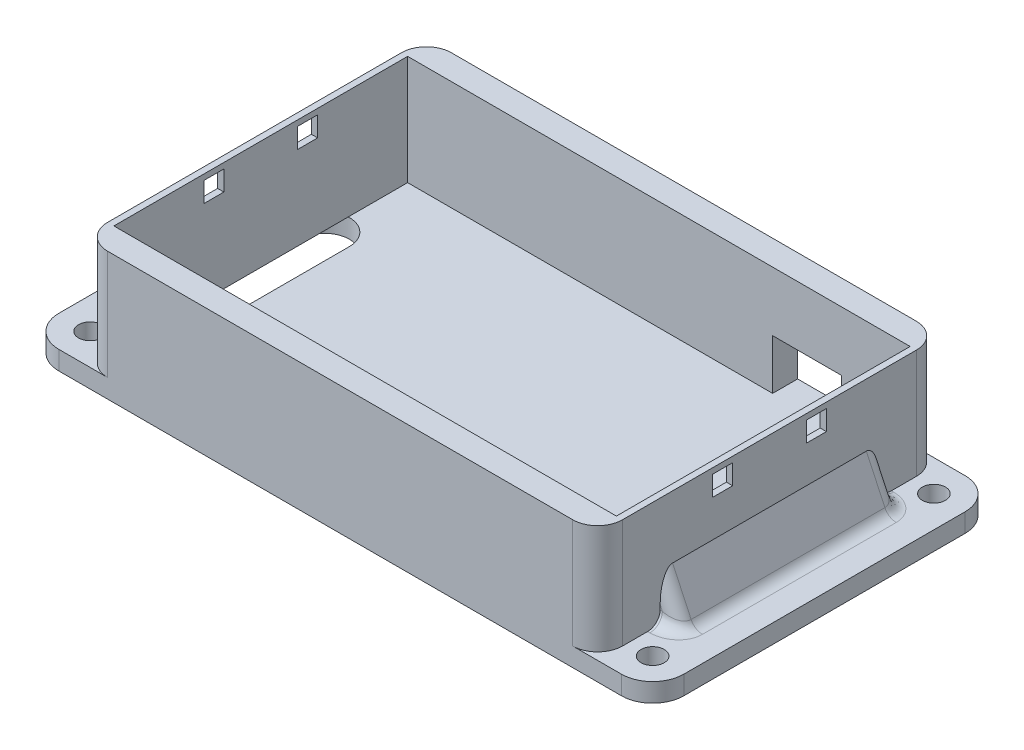
SolidWorks part; units mm, degrees
material "Copper"
ref_plane "Front Plane" through (0, 0, 0) normal (0, 0, 1) x (1, 0, 0)
ref_plane "Top Plane" through (0, 0, 0) normal (0, 1, 0) x (1, 0, 0)
ref_plane "Right Plane" through (0, 0, 0) normal (1, 0, 0) x (0, 0, -1)
sketch "Sketch1" plane through (0, 0, 0) normal (0, 1, 0) x (1, 0, 0)
  line L1 (6.35, 0) -> (120.65, 0)
  line L2 (0, 6.35) -> (0, 63.5)
  line L3 (6.35, 69.85) -> (120.65, 69.85)
  line L4 (127, 6.35) -> (127, 63.5)
  arc A0 (6.35, 0) -> (0, 6.35) centre (6.35, 6.35) cw
  arc A1 (120.65, 0) -> (127, 6.35) centre (120.65, 6.35) ccw
  arc A2 (120.65, 69.85) -> (127, 63.5) centre (120.65, 63.5) cw
  arc A3 (0, 63.5) -> (6.35, 69.85) centre (6.35, 63.5) cw
  point P7 (0, 0)
  point P10 (127, 0)
  point P13 (127, 69.85)
  point P16 (0, 69.85)
  dimension "D3" = 6.35
  dimension "D1" = 127
  dimension "D2" = 69.85
extrude "Base Extrude" add sketch "Sketch1" along normal blind 3.81
sketch "Sketch2" plane through (0, 3.81, 0) normal (0, 1, 0) x (1, 0, 0)
  line L0 (63.5, 69.85) -> (63.5, 0) construction
  line L1 (120.65, 69.85) -> (6.35, 69.85) construction
  line L2 (6.35, 0) -> (120.65, 0) construction
  line L3 (0, 34.925) -> (127, 34.925) construction
  line L4 (0, 63.5) -> (0, 6.35) construction
  line L5 (127, 6.35) -> (127, 63.5) construction
  line L6 (7.62, 34.925) -> (17.78, 34.925) construction
  line L8 (7.62, 47.625) -> (7.62, 22.225)
  line L10 (17.78, 47.625) -> (17.78, 22.225)
  line L11 (119.38, 47.625) -> (119.38, 22.225)
  line L12 (109.22, 47.625) -> (109.22, 22.225)
  circle A0 centre (6.35, 63.5) radius 2.3495
  circle A1 centre (6.35, 6.35) radius 2.3495
  arc A2 (17.78, 47.625) -> (7.62, 47.625) centre (12.7, 47.625) ccw
  arc A3 (7.62, 22.225) -> (17.78, 22.225) centre (12.7, 22.225) ccw
  circle A4 centre (120.65, 6.35) radius 2.3495
  circle A5 centre (120.65, 63.5) radius 2.3495
  arc A6 (109.22, 47.625) -> (119.38, 47.625) centre (114.3, 47.625) cw
  arc A7 (119.38, 22.225) -> (109.22, 22.225) centre (114.3, 22.225) cw
  dimension "D1" = 4.699
  dimension "D5" = 5.08
  dimension "D2" = 6.35
  dimension "D3" = 6.35
  dimension "D4" = 6.35
  dimension "D6" = 10.16
  dimension "D7" = 25.4
  dimension "D8" = 12.7
extrude "Hole Cuts" cut sketch "Sketch2" against normal through all
sketch "Sketch3" plane through (0, 3.81, 0) normal (0, 1, 0) x (1, 0, 0)
  line L0 (120.65, 69.85) -> (6.35, 69.85) construction
  line L1 (16.256, 69.85) -> (110.744, 69.85)
  line L2 (11.176, 64.77) -> (11.176, 5.08)
  line L3 (16.256, 0) -> (110.744, 0)
  line L4 (115.824, 64.77) -> (115.824, 5.08)
  line L5 (6.35, 0) -> (120.65, 0) construction
  line L6 (63.5, 69.85) -> (63.5, 0) construction
  line L7 (63.5, 0) -> (63.5, 69.85) construction
  line L9 (12.446, 64.77) -> (114.554, 64.77)
  line L10 (12.446, 64.77) -> (12.446, 5.08)
  line L11 (12.446, 5.08) -> (114.554, 5.08)
  line L12 (114.554, 64.77) -> (114.554, 5.08)
  arc A0 (110.744, 69.85) -> (115.824, 64.77) centre (110.744, 64.77) cw
  arc A1 (110.744, 0) -> (115.824, 5.08) centre (110.744, 5.08) ccw
  arc A2 (11.176, 5.08) -> (16.256, 0) centre (16.256, 5.08) ccw
  arc A3 (16.256, 69.85) -> (11.176, 64.77) centre (16.256, 64.77) ccw
  point P18 (115.824, 0)
  point P23 (11.176, 69.85)
  dimension "D6" = 5.08
  dimension "D1" = 104.648
  dimension "D2" = 1.27
  dimension "D3" = 1.27
  dimension "D4" = 5.08
  dimension "D5" = 5.08
extrude "Shell Extrude" add sketch "Sketch3" along normal blind 22.225
ref_plane "Shell Support Plane" through (0, 0, -34.925) normal (0, 0, 1) x (1, 0, 0)
sketch "Sketch4" plane through (0, 0, -34.925) normal (0, 0, 1) x (1, 0, 0)
  line L0 (11.176, 3.81) -> (6.731, 3.81)
  line L1 (6.731, 3.81) -> (11.176, 13.335)
  line L2 (11.176, 26.035) -> (11.176, 3.81) construction
  line L3 (11.176, 13.335) -> (11.176, 3.81)
  line L5 (63.5, 26.035) -> (63.5, 0) construction
  line L6 (16.256, 26.035) -> (110.744, 26.035) construction
  line L7 (6.35, 0) -> (120.65, 0) construction
  line L8 (115.824, 13.335) -> (115.824, 3.81)
  line L9 (120.269, 3.81) -> (115.824, 13.335)
  line L10 (115.824, 3.81) -> (120.269, 3.81)
  dimension "D1" = 4.445
  dimension "D2" = 9.525
extrude "Shell Support Extrude" add sketch "Sketch4" along normal blind 22.225 and the other way blind 22.225
fillet "Shell Support Fillet" radius 2.54 10 edges at (6.731, 3.81, -34.925) (8.9535, 3.81, -12.7) (8.9535, 8.5725, -12.7) (8.9535, 8.5725, -57.15) (8.9535, 3.81, -57.15) (118.0465, 8.5725, -57.15) (118.0465, 8.5725, -12.7) (118.0465, 3.81, -12.7) (120.269, 3.81, -34.925) (118.0465, 3.81, -57.15)
sketch "Sketch5" plane through (115.824, 0, 0) normal (1, 0, 0) x (0, 0, -1)
  line L0 (34.925, 26.035) -> (34.925, 0) construction
  line L1 (5.08, 26.035) -> (64.77, 26.035) construction
  line L2 (6.35, 0) -> (63.5, 0) construction
  line L3 (46.482, 24.892) -> (42.418, 20.828) construction
  line L4 (23.368, 20.828) -> (27.432, 20.828)
  line L5 (23.368, 20.828) -> (23.368, 24.892)
  line L6 (23.368, 24.892) -> (27.432, 24.892)
  line L7 (27.432, 20.828) -> (27.432, 24.892)
  line L8 (23.368, 20.828) -> (27.432, 24.892) construction
  line L9 (23.368, 24.892) -> (27.432, 20.828) construction
  line L10 (46.482, 20.828) -> (42.418, 24.892) construction
  line L11 (42.418, 20.828) -> (42.418, 24.892)
  line L12 (46.482, 24.892) -> (42.418, 24.892)
  line L13 (46.482, 20.828) -> (46.482, 24.892)
  line L14 (46.482, 20.828) -> (42.418, 20.828)
  dimension "D1" = 1.143
  dimension "D2" = 4.064
  dimension "D3" = 7.493
extrude "Cover Holes" cut sketch "Sketch5" against normal through all
sketch "Sketch6" plane through (0, 0, -69.85) normal (0, 0, -1) x (-1, 0, 0)
  line L0 (-120.65, 3.81) -> (-110.744, 3.81) construction
  line L1 (-100.584, 3.81) -> (-86.614, 3.81)
  line L2 (-100.584, 3.81) -> (-100.584, 13.97)
  line L3 (-100.584, 13.97) -> (-86.614, 13.97)
  line L4 (-86.614, 3.81) -> (-86.614, 13.97)
  line L5 (-110.744, 26.035) -> (-110.744, 3.81) construction
  dimension "D1" = 10.16
  dimension "D2" = 13.97
  dimension "D3" = 10.16
extrude "Battrey Wire Hole" cut sketch "Sketch6" against normal up to next
